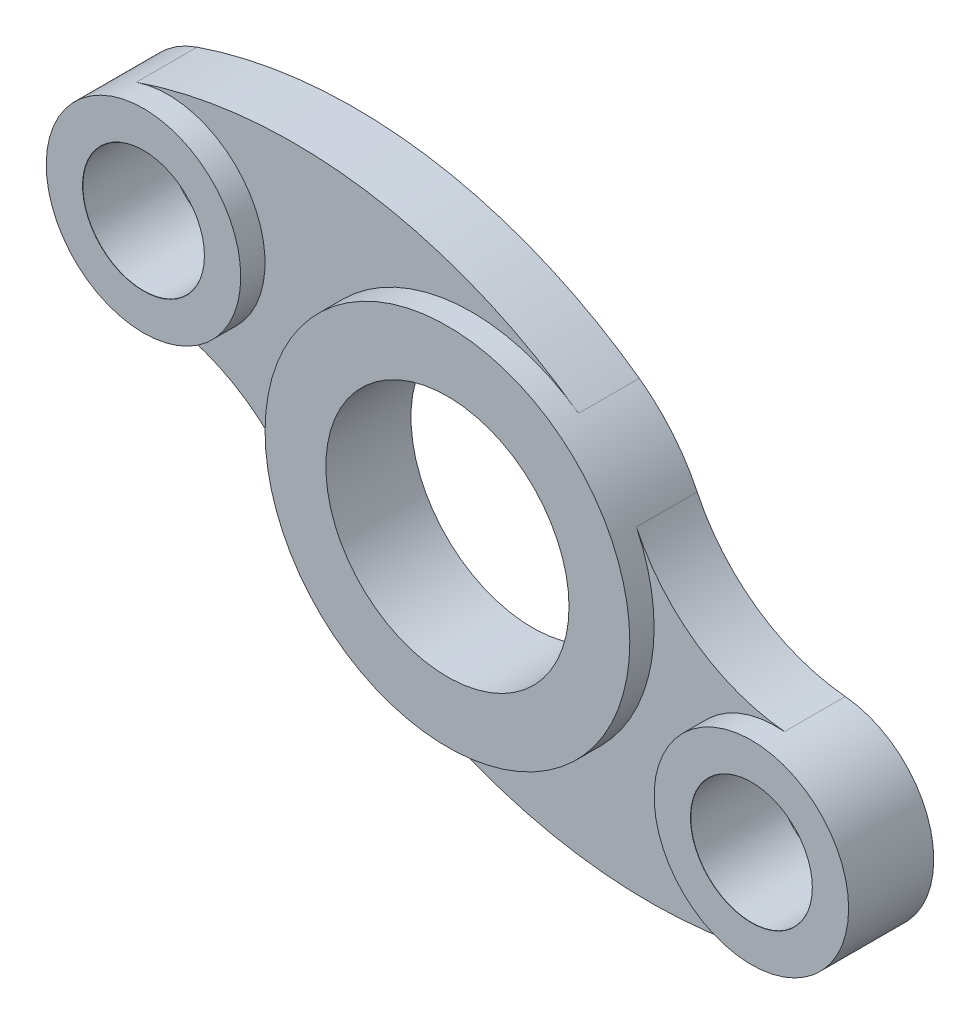
SolidWorks part; units mm, degrees
ref_plane "Piano frontale" through (0, 0, 0) normal (0, 0, 1) x (1, 0, 0)
ref_plane "Piano superiore" through (0, 0, 0) normal (0, 1, 0) x (1, 0, 0)
ref_plane "Piano destro" through (0, 0, 0) normal (1, 0, 0) x (0, 0, -1)
sketch "Schizzo1" plane through (0, 0, 0) normal (0, 0, 1) x (1, 0, 0)
  line L0 (0, 33.7218) -> (0, -32.4396) construction
  line L1 (-64.7511, 0) -> (56.5414, 0) construction
  line L2 (-50, 36.7187) -> (-50, 4) construction
  line L3 (-66.7436, 20) -> (-43.2848, 20) construction
  line L4 (50, -3.8984) -> (50, -36.7187) construction
  line L5 (38.279, -20) -> (59.0714, -20) construction
  circle A0 centre (0, 0) radius 30
  circle A1 centre (50, -20) radius 16
  circle A2 centre (-50, 20) radius 16
  arc A3 (-51.4485, 4.0657) -> (-27.0822, -12.9056) centre (-54.1644, -25.8111) cw
  arc A4 (51.4485, -4.0657) -> (27.0822, 12.9056) centre (54.1644, 25.8111) cw
  arc A5 (-55.1854, 35.1364) -> (20.7119, 21.9282) centre (-29.2583, -40.5457) cw
  arc A6 (55.1854, -35.1364) -> (-17.555, -24.3274) centre (29.2583, 40.5457) cw
  circle A7 centre (0, 0) radius 20
  point P15 (-50, 20)
  point P21 (50, -20)
  point P23 (0.9224, 0)
  dimension "D5" = 60
  dimension "D6" = 32
  dimension "D7" = 32
  dimension "D8" = 30
  dimension "D9" = 30
  dimension "D10" = 80
  dimension "D11" = 80
  dimension "D12" = 40
  dimension "D1" = 20
  dimension "D2" = 20
  dimension "D3" = 50
  dimension "D4" = 50
extrude "Estrusione-Estrusione1" add sketch "Schizzo1" along normal blind 14 from offset 5 contours A2 offset against normal yes
extrude "Estrusione-Estrusione3" add sketch "Schizzo1<4>" along normal blind 14 from offset 5 separate body contours A1 offset against normal yes
sketch "Schizzo1<4>" plane through (0, 0, 0) normal (0, 0, 1) x (1, 0, 0) same geometry as "Schizzo1"
extrude "Estrusione-Estrusione5" add sketch "Schizzo1<7>" along normal blind 14 from offset 5 separate body contours A0 offset against normal yes
sketch "Schizzo1<7>" plane through (0, 0, 0) normal (0, 0, 1) x (1, 0, 0) same geometry as "Schizzo1"
extrude "Estrusione-Estrusione6" add sketch "Schizzo1<11>" along normal mid plane 10 from offset 0 contours A6 A1 A4 A0 region at (26.1262, -23.9298, 0)
sketch "Schizzo1<11>" plane through (0, 0, 0) normal (0, 0, 1) x (1, 0, 0) same geometry as "Schizzo1"
extrude "Estrusione-Estrusione7" add sketch "Schizzo1<12>" along normal mid plane 10 contours A5 A2 A3 A0 region at (-26.1262, 23.9298, 0)
sketch "Schizzo1<12>" plane through (0, 0, 0) normal (0, 0, 1) x (1, 0, 0) same geometry as "Schizzo1"
hole_wizard "Foro Ø20.0 (20)-1" positions "Schizzo3D2" profile "Schizzo2" hole size "Ø20.0" standard "ISO" end condition up to next
sketch3d "Schizzo3D2"
  point P6 (-50, 20, 9)
  point P10 (50, -20, 9)
  point P13 (0, 0, 0)
sketch "Schizzo2" plane through (-50, 20, 9) normal (1, 0, 0) x (0, -1, 0)
  line L0 (0, 0) -> (0, 14)
  line L1 (0, 14) -> (10, 14)
  line L2 (10, 14) -> (10, 0.025)
  line L3 (10, 0.025) -> (10.025, 0)
  line L5 (10.025, 0) -> (0, 0)
  line L6 (-10, 0.025) -> (-10.025, 0) construction
  line L11 (0, -6.35) -> (0, 107.95) construction
  dimension "Thru Hole Dia." = 20
  dimension "Thru Hole Depth" = 14
  dimension "Near C'Sink Dia." = 20.05
  dimension "Near C'Sink Angle" = 90
extrude "Taglio-Estrusione1" cut sketch "Schizzo1<13>" against normal through all from offset 9 contours A7
sketch "Schizzo1<13>" plane through (0, 0, 0) normal (0, 0, 1) x (1, 0, 0) same geometry as "Schizzo1"
